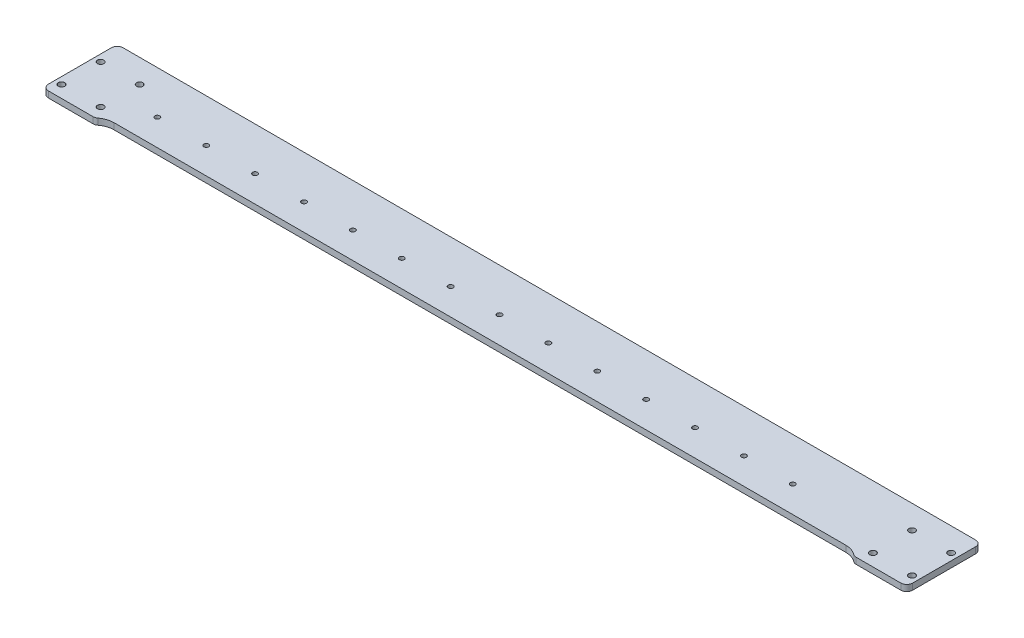
SolidWorks part; units mm, degrees
material "AISI 1045 Steel, cold drawn"
ref_plane "Front Plane" through (0, 0, 0) normal (0, 0, 1) x (1, 0, 0)
ref_plane "Top Plane" through (0, 0, 0) normal (0, 1, 0) x (1, 0, 0)
ref_plane "Right Plane" through (0, 0, 0) normal (1, 0, 0) x (0, 0, -1)
sketch "Sketch1" plane through (0, 0, 0) normal (0, 1, 0) x (1, 0, 0)
  line L0 (0, 0) -> (194, 0)
  line L1 (194, 0) -> (194, -2.7)
  line L2 (194, -2.7) -> (221, -2.7)
  line L3 (221, -2.7) -> (221, 29.7)
  line L4 (221, 29.7) -> (0, 29.7) construction
  line L7 (0, 0) -> (0, 29.7)
  line L8 (221, 13.5) -> (0, 13.5) construction
  line L9 (221, 29.7) -> (221, 35.5)
  line L10 (221, 35.5) -> (0, 35.5)
  line L11 (0, 35.5) -> (0, 29.7)
  dimension "D1" = 194
  dimension "D2" = 27
  dimension "D3" = 29.7
  dimension "D4" = 32.4
  dimension "D5" = 22
extrude "Boss-Extrude1" add sketch "Sketch1" along normal blind 3.175
hole_wizard "M3 Clearance Hole1" positions "Sketch2" profile "Sketch3" hole size "M3" standard "ANSI Metric" end condition through all
sketch "Sketch2" plane through (0, 3.175, 0) normal (0, 1, 0) x (1, 0, 0)
  line L1 (217.5, 3.5) -> (197.5, 3.5)
  line L2 (217.5, 3.5) -> (217.5, 23.5)
  line L3 (217.5, 23.5) -> (197.5, 23.5)
  line L4 (197.5, 3.5) -> (197.5, 23.5)
  line L5 (217.5, 3.5) -> (197.5, 23.5) construction
  line L6 (217.5, 23.5) -> (197.5, 3.5) construction
  line L10 (207.5, 13.5) -> (207.5, -2.7) construction
  line L13 (194, -2.7) -> (221, -2.7) construction
  line L17 (0, 0) -> (194, 0) construction
  point P2 (197.5, 23.5)
  point P35 (217.5, 3.5)
  point P36 (217.5, 23.5)
  point P37 (197.5, 3.5)
  dimension "D1" = 20
  dimension "D2" = 13.5
sketch "Sketch3" plane through (197.5, 3.175, -23.5) normal (1, 0, 0) x (0, 0, 1)
  line L0 (0, 0) -> (0, 3.175)
  line L1 (0, 3.175) -> (1.6, 3.175)
  line L2 (1.6, 3.175) -> (1.6, 0.025)
  line L3 (1.6, 0.025) -> (1.625, 0)
  line L5 (1.625, 0) -> (0, 0)
  line L6 (-1.6, 0.025) -> (-1.625, 0) construction
  line L11 (0, -6.35) -> (0, 107.95) construction
  dimension "Thru Hole Dia." = 3.2
  dimension "Thru Hole Depth" = 3.175
  dimension "Near C'Sink Dia." = 3.25
  dimension "Near C'Sink Angle" = 90
fillet "Fillet1" radius 10 1 edges at (194, 1.5875, 0)
fillet "Fillet2" radius 3 3 edges at (221, 1.5875, 2.7) (194, 1.5875, 2.7) (221, 1.5875, -35.5)
mirror "Mirror1" about plane through (0, 3.175, -35.5) normal (1, 0, 0) of bodies 103
hole_wizard "Tap Drill for M3x0.5 Tap2" positions "Sketch6" profile "Sketch7" hole size "M3x0.5" standard "ANSI Metric" end condition through all
sketch "Sketch6" plane through (0, 0, 0) normal (0, -1, 0) x (-1, 0, 0)
  line L0 (187.1655, 0) -> (-187.1655, 0) construction
  line L2 (221, 0.3) -> (221, 32.5) construction
  point P11 (178.5, 13.5)
  dimension "D1" = 13.5
  dimension "D2" = 42.5
sketch "Sketch7" plane through (-178.5, 0, -13.5) normal (1, 0, 0) x (0, 0, -1)
  line L0 (0, 0) -> (0, 3.175)
  line L1 (0, 3.175) -> (1.25, 3.175)
  line L2 (1.25, 3.175) -> (1.25, 0.025)
  line L3 (1.25, 0.025) -> (1.275, 0)
  line L5 (1.275, 0) -> (0, 0)
  line L6 (-1.25, 0.025) -> (-1.275, 0) construction
  line L11 (0, -6.35) -> (0, 107.95) construction
  dimension "Thru Hole Dia." = 2.5
  dimension "Thru Hole Depth" = 3.175
  dimension "Near C'Sink Dia." = 2.55
  dimension "Near C'Sink Angle" = 90
pattern_linear "LPattern1" count 14 spacing 25 along (1, 0, 0) of "Tap Drill for M3x0.5 Tap2"
